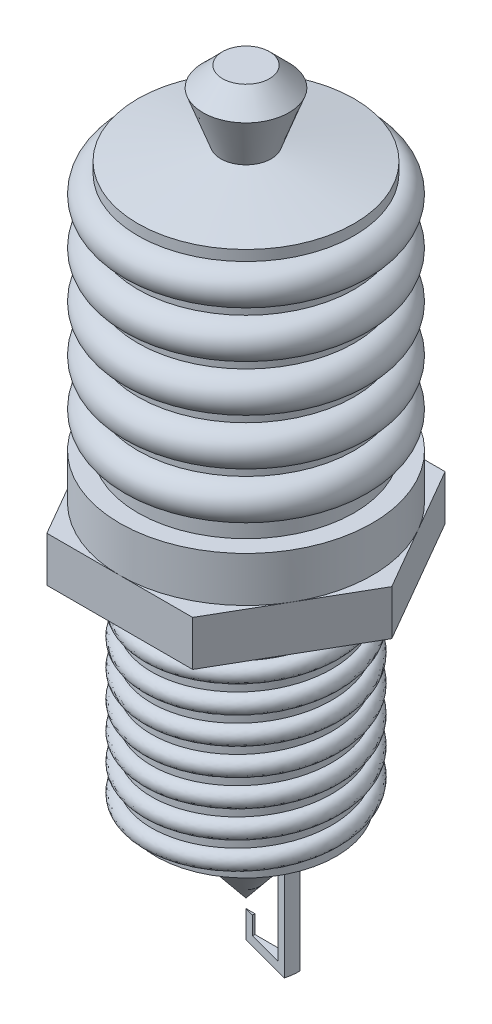
SolidWorks part; units mm, degrees
ref_plane "Front Plane" through (0, 0, 0) normal (0, 0, 1) x (1, 0, 0)
ref_plane "Top Plane" through (0, 0, 0) normal (0, 1, 0) x (1, 0, 0)
ref_plane "Right Plane" through (0, 0, 0) normal (1, 0, 0) x (0, 0, -1)
sketch "Sketch1" plane through (0, 0, 0) normal (0, 0, 1) x (1, 0, 0)
  line L0 (0, 1016) -> (0, 0)
  line L1 (0, 0) -> (92.71, 114.3)
  line L2 (92.71, 114.3) -> (127, 114.3)
  line L3 (127, 114.3) -> (127, 419.1)
  line L4 (127, 419.1) -> (88.9, 419.1)
  line L5 (88.9, 419.1) -> (88.9, 546.1)
  line L6 (88.9, 546.1) -> (152.4, 546.1)
  line L7 (0, 1016) -> (33.02, 1016)
  line L8 (33.02, 1016) -> (60.6382, 988.3818)
  line L9 (60.6382, 988.3818) -> (35.56, 919.48)
  line L10 (35.56, 919.48) -> (152.4, 898.878)
  line L11 (152.4, 898.878) -> (152.4, 884.146)
  line L12 (152.4, 833.346) -> (152.4, 818.614)
  line L13 (152.4, 767.814) -> (152.4, 753.082)
  line L14 (152.4, 702.282) -> (152.4, 687.55)
  line L15 (152.4, 636.75) -> (152.4, 622.018)
  line L16 (152.4, 546.1) -> (152.4, 571.218)
  arc A0 (152.4, 884.146) -> (152.4, 833.346) centre (152.4, 858.746) cw
  arc A1 (152.4, 818.614) -> (152.4, 767.814) centre (152.4, 793.214) cw
  arc A2 (152.4, 753.082) -> (152.4, 702.282) centre (152.4, 727.682) cw
  arc A3 (152.4, 687.55) -> (152.4, 636.75) centre (152.4, 662.15) cw
  arc A4 (152.4, 622.018) -> (152.4, 571.218) centre (152.4, 596.618) cw
  dimension "D15" = 25.4
  dimension "D1" = 1016
  dimension "D2" = 92.71
  dimension "D3" = 114.3
  dimension "D4" = 304.8
  dimension "D5" = 127
  dimension "D6" = 88.9
  dimension "D7" = 33.02
  dimension "D8" = 35.56
  dimension "D9" = 96.52
  dimension "D10" = 65
  dimension "D11" = 80
  dimension "D12" = 135
  dimension "D13" = 152.4
  dimension "D14" = 14.732
  dimension "D17" = 127
  dimension "D16" = 5
revolve "Revolve1" add sketch "Sketch1" angle 360 about L0
sketch "Sketch2" plane through (0, 419.1, 0) normal (0, 1, 0) x (1, 0, 0)
  line L1 (102.6529, 177.8) -> (-102.6529, 177.8)
  line L2 (-102.6529, 177.8) -> (-205.3058, 0)
  line L3 (-205.3058, 0) -> (-102.6529, -177.8)
  line L4 (-102.6529, -177.8) -> (102.6529, -177.8)
  line L5 (102.6529, -177.8) -> (205.3058, 0)
  line L6 (205.3058, 0) -> (102.6529, 177.8)
  circle A0 centre (0, 0) radius 177.8 construction
  point P1 (0, 0)
  dimension "D1" = 355.6
extrude "Boss-Extrude1" add sketch "Sketch2" along normal blind 63.5
fillet "Fillet3" radius 50.8 1 edges at (0, 114.3, 92.71)
sketch "Sketch3" plane through (0, 482.6, 0) normal (0, 1, 0) x (1, 0, 0)
  circle A0 centre (0, 0) radius 177.8
  dimension "D1" = 355.6
extrude "Boss-Extrude2" add sketch "Sketch3" along normal blind 63.5
sketch "Sketch4" plane through (0, 114.3, 0) normal (0, -1, 0) x (1, 0, 0)
  circle A0 centre (0, 0) radius 127
  dimension "D1" = 254
curve "Helix/Spiral1" pitch 38.1 height 295.275 turns 7.75
ref_plane "Plane2" through (127, 409.575, 0) normal (0, 0.0477, -0.9989) x (-1, 0, 0)
sketch "Sketch10" plane through (127, 409.575, 0) normal (0, 0.0477, -0.9989) x (-1, 0, 0)
  line L0 (0, 9.5142) -> (0, -294.939) construction
  circle A0 centre (0, 0.0494) radius 12.7
  dimension "D1" = 25.4
sweep "Sweep1" add profiles "Sketch10" path "Helix/Spiral1"
sketch "Sketch11" plane through (0, 0, 0) normal (0, 0, 1) x (1, 0, 0)
  line L0 (0, -12.7) -> (0, -50.8)
  line L1 (0, -50.8) -> (76.2, -50.8)
  line L2 (76.2, -50.8) -> (76.2, 114.3)
  line L3 (-116.9154, 114.3) -> (116.9154, 114.3) construction
  dimension "D1" = 76.2
  dimension "D2" = 165.1
  dimension "D3" = 38.1
revolve "Revolve-Thin1" add sketch "Sketch11" angle 15 about L0 wall 12.7
